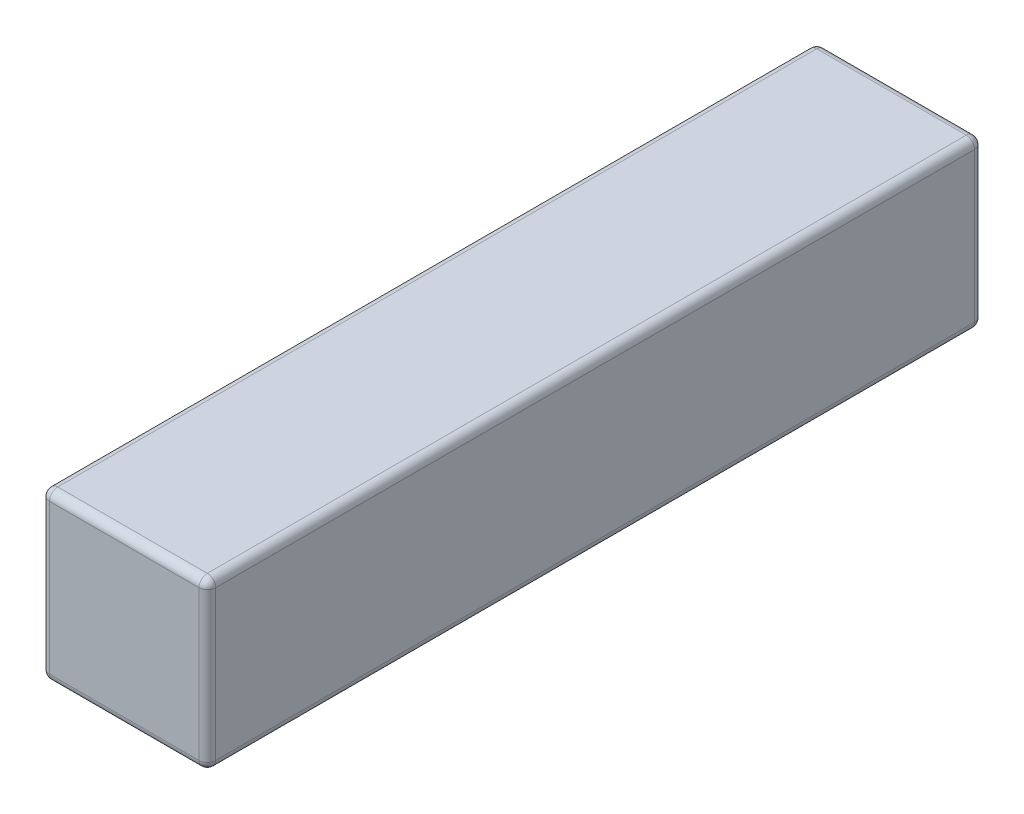
SolidWorks part; units mm, degrees
ref_plane "Front Plane" through (0, 0, 0) normal (0, 0, 1) x (1, 0, 0)
ref_plane "Top Plane" through (0, 0, 0) normal (0, 1, 0) x (1, 0, 0)
ref_plane "Right Plane" through (0, 0, 0) normal (1, 0, 0) x (0, 0, -1)
sketch "Sketch1" plane through (0, 0, 0) normal (0, 0, 1) x (1, 0, 0)
  line L3 (1.5, -1.5) -> (-1.5, -1.5)
  line L4 (1.5, -1.5) -> (1.5, 1.5)
  line L5 (1.5, 1.5) -> (-1.5, 1.5)
  line L6 (-1.5, -1.5) -> (-1.5, 1.5)
  line L7 (1.5, -1.5) -> (-1.5, 1.5) construction
  line L8 (1.5, 1.5) -> (-1.5, -1.5) construction
  point P0 (0, 0)
  dimension "Width" = 3
  dimension "Height" = 3
sketch "Sketch2" plane through (0, 0, 0) normal (1, 0, 0) x (0, 0, -1)
  line L2 (7, -1.5) -> (-7, -1.5)
  line L3 (7, -1.5) -> (7, 1.5)
  line L4 (7, 1.5) -> (-7, 1.5)
  line L5 (-7, -1.5) -> (-7, 1.5)
  line L6 (7, -1.5) -> (-7, 1.5) construction
  line L7 (7, 1.5) -> (-7, -1.5) construction
  point P0 (0, 0)
  point P4 (0, 0)
  dimension "Length" = 14
sketch "Sketch3" plane through (0, 0, 0) normal (0, 0, 1) x (1, 0, 0)
  line L0 (1.5, -1.5) -> (1.5, 1.5) construction
  line L5 (1.5, -1.5) -> (-1.5, -1.5) construction
  line L6 (-1.5, -1.5) -> (-1.5, 1.5) construction
  line L7 (1.5, 1.5) -> (-1.5, 1.5) construction
  line L8 (1.5, -1.5) -> (1.5, 1.5)
  line L9 (1.5, -1.5) -> (-1.5, -1.5)
  line L10 (-1.5, -1.5) -> (-1.5, 1.5)
  line L11 (1.5, 1.5) -> (-1.5, 1.5)
extrude "Boss-Extrude1" add sketch "Sketch3" along normal up to vertex (7 mm away) and the other way up to vertex (7 mm away) up to point (0, 1.5, 7) other way up to point (0, 1.5, -7)
fillet "Fillet2" radius 0.15 12 edges at (-1.5, 0, -7) (0, -1.5, -7) (-1.5, 1.5, 0) (0, 1.5, -7) (1.5, 1.5, 0) (1.5, 0, -7) (1.5, -1.5, 0) (-1.5, 0, 7) (0, 1.5, 7) (1.5, 0, 7) (0, -1.5, 7) (-1.5, -1.5, 0)
ref_plane "Contact Plane 1" through (0, 0, 7) normal (0, 0, 1) x (1, 0, 0)
ref_plane "Contact Plane 2" through (0, 0, -7) normal (0, 0, 1) x (1, 0, 0)
ref_axis "Center Axis 1" through (0, 0, -4.4) along (0, 0, 1)
